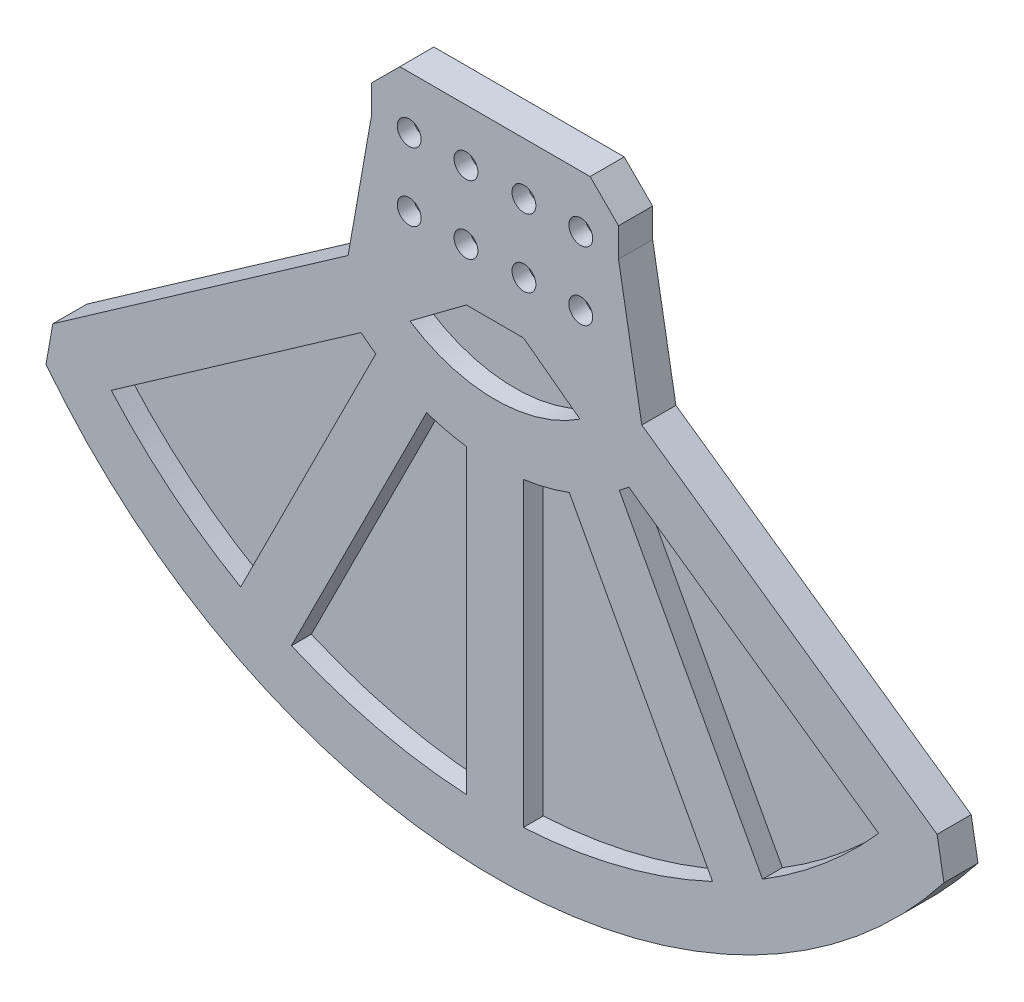
SolidWorks part; units mm, degrees
ref_plane "정면" through (0, 0, 0) normal (0, 0, 1) x (1, 0, 0)
ref_plane "윗면" through (0, 0, 0) normal (0, 1, 0) x (1, 0, 0)
ref_plane "우측면" through (0, 0, 0) normal (1, 0, 0) x (0, 0, -1)
sketch "스케치1" plane through (0, 0, 0) normal (0, 0, 1) x (1, 0, 0)
  line L0 (0, 0) -> (0, 13.0127) construction
  line L1 (21.75, 21.23) -> (-21.75, 21.23)
  line L2 (-21.75, 21.23) -> (-21.75, -9.23)
  line L3 (21.75, 21.23) -> (21.75, -9.23)
  line L4 (-21.75, -9.23) -> (21.75, -9.23)
  line L5 (-5.1, 12) -> (5.1, 0) construction
  line L6 (-5.1, 0) -> (5.1, 12) construction
  line L7 (0, 6) -> (-81.9143, -51.3589)
  line L8 (0, 6) -> (81.9143, -51.3589)
  line L9 (0, 6) -> (0, -84) construction
  line L10 (0, 6) -> (-40.3475, -74.4492) construction
  line L11 (0, 6) -> (42.7574, -73.1947) construction
  line L22 (-5, -30.8) -> (-5, -83.861)
  line L28 (5, -30.8) -> (5, -83.861)
  line L30 (-12.0282, -29.1363) -> (-35.8158, -76.5665)
  line L33 (-20.967, -24.6532) -> (-44.7546, -72.0835)
  line L35 (-23.5619, -22.7067) -> (-67.5305, -53.4948)
  line L36 (13.0833, -28.7572) -> (38.2916, -75.4478)
  line L37 (23.5619, -22.7067) -> (67.5305, -53.4948)
  line L38 (21.8827, -24.0064) -> (47.0911, -70.697)
  line L39 (-5.0291, -9.23) -> (-14.9613, -16.6415)
  line L41 (5.0291, -9.23) -> (14.9613, -16.6415)
  circle A0 centre (-5.1, 0) radius 1.1
  circle A1 centre (5.1, 0) radius 1.1
  circle A2 centre (-15.1, 0) radius 1.1
  circle A3 centre (15.1, 0) radius 1.1
  circle A4 centre (-15.1, 12) radius 1.1
  circle A5 centre (-5.1, 12) radius 1.1
  circle A6 centre (5.1, 12) radius 1.1
  circle A7 centre (15.1, 12) radius 1.1
  arc A8 (-81.9143, -51.3589) -> (81.9143, -51.3589) centre (0, 6) ccw
  arc A10 (-23.5619, -22.7067) -> (-20.967, -24.6532) centre (0, 6) ccw
  arc A11 (-67.5305, -53.4948) -> (-44.7546, -72.0835) centre (0, 6) ccw
  arc A12 (-73.7229, -45.623) -> (73.7229, -45.623) centre (0, 6) ccw construction
  arc A13 (-35.8158, -76.5665) -> (-5, -83.861) centre (0, 6) ccw
  arc A14 (5, -83.861) -> (38.2916, -75.4478) centre (0, 6) ccw
  arc A15 (47.0911, -70.697) -> (67.5305, -53.4948) centre (0, 6) ccw
  arc A16 (5, -30.8) -> (13.0833, -28.7572) centre (0, 6) ccw
  arc A18 (-12.0282, -29.1363) -> (-5, -30.8) centre (0, 6) ccw
  arc A19 (21.8827, -24.0064) -> (23.5619, -22.7067) centre (0, 6) ccw
  arc A20 (-14.9613, -16.6415) -> (14.9613, -16.6415) centre (0, 6) ccw
  point P22 (0, 21.23)
  point P24 (0, -9.23)
  point P26 (0, 0)
  point P29 (0, 0)
  point P31 (0, 0)
  point P37 (-20.967, -23.7032)
  point P38 (-22.6847, -22.4548)
  point P39 (-5.0291, -29.85)
  point P40 (22.6847, -22.4548)
  point P41 (0, 0)
  dimension "D3" = 2.2
  dimension "D9" = 200
  dimension "D19" = 27.1381
  dimension "D23" = 10
  dimension "D24" = 10
  dimension "D25" = 5
  dimension "D2" = 10
  dimension "D5" = 12
  dimension "D6" = 43.5
  dimension "D7" = 9.23
  dimension "D8" = 9.23
  dimension "D10" = 26.635
  dimension "D11" = 10
  dimension "D13" = 10
  dimension "D14" = 10
  dimension "D15" = 10
  dimension "D16" = 10
  dimension "D17" = 36.731
  dimension "D18" = 36.731
  dimension "D20" = 5.0291
  dimension "D21" = 5.0291
  dimension "D22" = 26.634
  dimension "D26" = 5
  dimension "D27" = 5
  dimension "D28" = 6.65
  dimension "D12" = 10
  dimension "D4" = 2
extrude "보스-돌출1" add sketch "스케치1" along normal blind 6 contours A20 L39 L4 L7 A8 L8 L41 A11 L35 A10 L33 L28 A16 L36 A14 L30 A18 L22 A13 L38 A19 L37 A15 | L8 L7 L4 A0 A1 | L7 L8 L3 L1 L2 A6 A5 A4 A2 A3 A7 region at (0, 9.417, 0) region at (0.1721, -52.0763, 0) region at (0, -4.2509, 0)
extrude "보스-돌출2" add sketch "스케치1<3>" along normal blind 2.5 contours L35 A11 L33 A10 | A18 L30 A13 L22 | A16 L28 A14 L36 | A19 L38 A15 L37 | L39 A20 L41 L4 region at (0, -15.4193, 0) region at (-15.8517, -60.9661, 0) region at (16.8056, -60.5011, 0) region at (-44.0745, -48.8676, 0) region at (45.2248, -48.5654, 0)
sketch "스케치1<3>" plane through (0, 0, 0) normal (0, 0, 1) x (1, 0, 0) same geometry as "스케치1"
sketch "스케치2" plane through (0, 0, 6) normal (0, 0, 1) x (1, 0, 0)
  circle A0 centre (-15.1, 12) radius 2.1
  circle A1 centre (-5.1, 12) radius 2.1
  circle A2 centre (5.1, 12) radius 2.1
  circle A3 centre (15.1, 12) radius 2.1
  circle A4 centre (15.1, 0) radius 2.1
  circle A5 centre (5.1, 0) radius 2.1
  circle A6 centre (-5.1, 0) radius 2.1
  circle A7 centre (-15.1, 0) radius 2.1
  dimension "D1" = 4.2
extrude "컷-돌출1" cut sketch "스케치2" against normal blind 2.8
chamfer "모따기1" distance 5 angle 45 2 edges at (-21.75, 21.23, 3) (21.75, 21.23, 3)
chamfer "모따기2" distance 5 angle 45 4 edges at (-21.75, -9.23, 3) (21.75, -9.23, 3) (81.9143, -51.3589, 3) (-81.9143, -51.3589, 3) first distance on face at (-51.8322, -30.2944, 3) first distance on face at (51.8322, -30.2944, 3)
